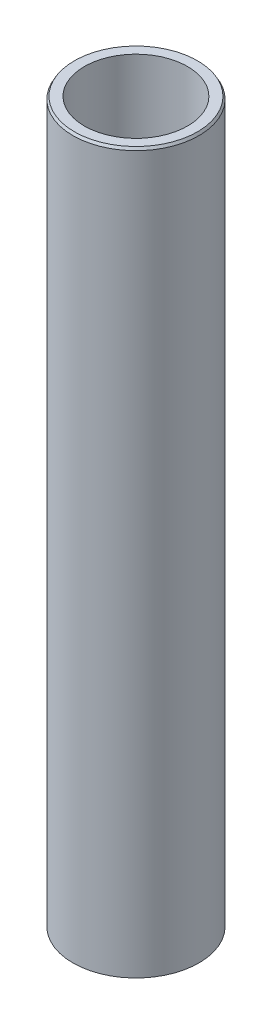
SolidWorks part; units mm, degrees
ref_plane "Front Plane" through (0, 0, 0) normal (0, 0, 1) x (1, 0, 0)
ref_plane "Top Plane" through (0, 0, 0) normal (0, 1, 0) x (1, 0, 0)
ref_plane "Right Plane" through (0, 0, 0) normal (1, 0, 0) x (0, 0, -1)
sketch "Sketch1" plane through (0, 0, 0) normal (0, 1, 0) x (1, 0, 0)
  circle A0 centre (0, 0) radius 52.5
  dimension "SHAFT_OD" = 105
extrude "Boss-Extrude1" add sketch "Sketch1" along normal blind 600
sketch "Sketch2" plane through (0, 0, 0) normal (0, 1, 0) x (1, 0, 0)
  circle A0 centre (0, 0) radius 42.9667
  dimension "BORE_D" = 85.9333
extrude "Cut-Extrude1" cut sketch "Sketch2" along normal through all
chamfer "Chamfer1" distance 2.1428 angle 30 2 edges at (0, 600, 52.5) (0, 0, 52.5) first distance on face at (0, 600, 52.5) first distance on face at (0, 0, 42.9667)
